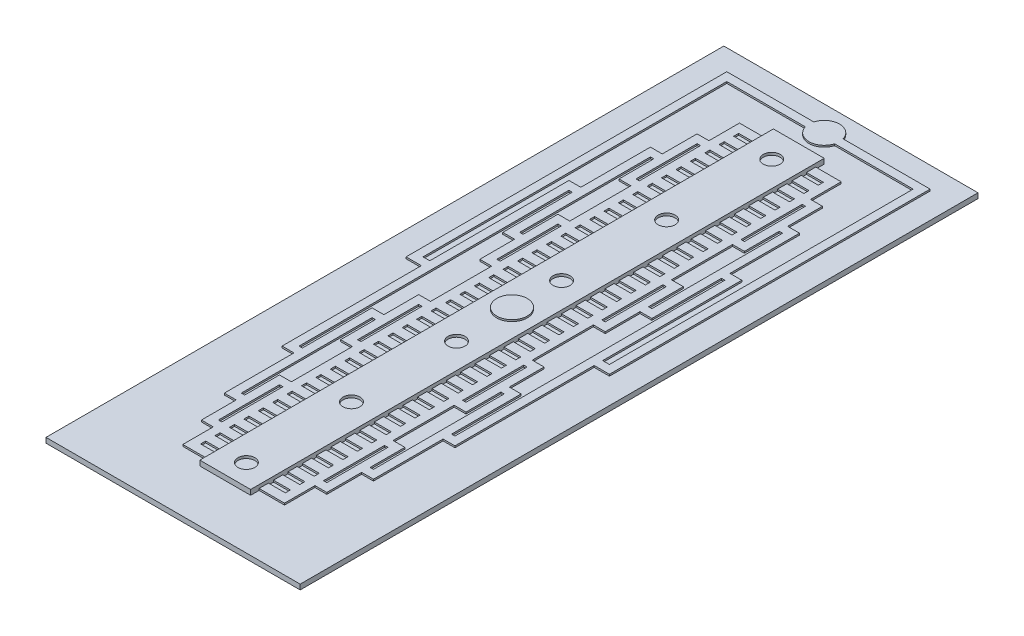
SolidWorks part; units mm, degrees
ref_plane "Front Plane" through (0, 0, 0) normal (0, 0, 1) x (1, 0, 0)
ref_plane "Top Plane" through (0, 0, 0) normal (0, 1, 0) x (1, 0, 0)
ref_plane "Right Plane" through (0, 0, 0) normal (1, 0, 0) x (0, 0, -1)
sketch "Sketch2" plane through (0, 0, 0) normal (0, 1, 0) x (1, 0, 0)
  line L1 (-7.5, 20) -> (7.5, 20)
  line L2 (-7.5, 20) -> (-7.5, -20)
  line L3 (-7.5, -20) -> (7.5, -20)
  line L4 (7.5, 20) -> (7.5, -20)
  line L5 (-7.5, 20) -> (7.5, -20) construction
  line L6 (-7.5, -20) -> (7.5, 20) construction
  point P0 (0, 0)
extrude "Boss-Extrude1" add sketch "Sketch2" along normal blind 0.3
sketch "Sketch3" plane through (0, 0.3, 0) normal (0, 1, 0) x (1, 0, 0)
  line L1 (-1.5, 16.925) -> (1.5, 16.925)
  line L2 (-1.5, 16.925) -> (-1.5, -16.925)
  line L3 (-1.5, -16.925) -> (1.5, -16.925)
  line L4 (1.5, 16.925) -> (1.5, -16.925)
  line L5 (-1.5, 16.925) -> (1.5, -16.925) construction
  line L6 (-1.5, -16.925) -> (1.5, 16.925) construction
  point P0 (0, 0)
extrude "Boss-Extrude2" add sketch "Sketch3" along normal blind 0.3
sketch "Sketch4" plane through (0, 0.3, 0) normal (0, 1, 0) x (1, 0, 0)
  line L0 (0, 19.2283) -> (0, -19.2283) construction
  line L1 (-7.7467, 0) -> (7.7467, 0) construction
  line L2 (1.5, 16.425) -> (3, 16.425)
  line L3 (1.5, 16.425) -> (1.5, -16.425)
  line L4 (3, 16.425) -> (3, -16.425)
  line L5 (1.5, -16.425) -> (3, -16.425)
  line L6 (1.5, -16.925) -> (1.5, 16.925) construction
  line L7 (-1.5, -16.425) -> (-3, -16.425)
  line L8 (-1.5, 16.425) -> (-1.5, -16.425)
  line L9 (-3, 16.425) -> (-3, -16.425)
  line L10 (-1.5, 16.425) -> (-3, 16.425)
  point P3 (3, 0)
  point P4 (0, 0)
  point P8 (0, 0)
extrude "Boss-Extrude3" add sketch "Sketch4" along normal blind 0.1
sketch "Sketch5" plane through (0, 0.4, 0) normal (0, 1, 0) x (1, 0, 0)
  line L0 (1.5, 16.425) -> (1.5, -16.425) construction
  line L1 (1.5, 15.875) -> (2.5, 15.875)
  line L2 (1.5, 15.875) -> (1.5, 15.575)
  line L3 (2.5, 15.875) -> (2.5, 15.575)
  line L4 (1.5, 15.575) -> (2.5, 15.575)
  line L5 (-1.5, 15.875) -> (-1.5, 15.575)
  line L6 (-2.5, 15.875) -> (-1.5, 15.875)
  line L7 (-2.5, 15.875) -> (-2.5, 15.575)
  line L8 (-2.5, 15.575) -> (-1.5, 15.575)
  line L9 (-1.5, 15.025) -> (-1.5, 14.725)
  line L10 (-2.5, 15.025) -> (-1.5, 15.025)
  line L11 (-2.5, 15.025) -> (-2.5, 14.725)
  line L12 (-2.5, 14.725) -> (-1.5, 14.725)
  line L13 (-1.5, 14.175) -> (-1.5, 13.875)
  line L14 (-2.5, 14.175) -> (-1.5, 14.175)
  line L15 (-2.5, 14.175) -> (-2.5, 13.875)
  line L16 (-2.5, 13.875) -> (-1.5, 13.875)
  line L17 (-1.5, 13.325) -> (-1.5, 13.025)
  line L18 (-2.5, 13.325) -> (-1.5, 13.325)
  line L19 (-2.5, 13.325) -> (-2.5, 13.025)
  line L20 (-2.5, 13.025) -> (-1.5, 13.025)
  line L21 (-1.5, 12.475) -> (-1.5, 12.175)
  line L22 (-2.5, 12.475) -> (-1.5, 12.475)
  line L23 (-2.5, 12.475) -> (-2.5, 12.175)
  line L24 (-2.5, 12.175) -> (-1.5, 12.175)
  line L25 (-1.5, 11.625) -> (-1.5, 11.325)
  line L26 (-2.5, 11.625) -> (-1.5, 11.625)
  line L27 (-2.5, 11.625) -> (-2.5, 11.325)
  line L28 (-2.5, 11.325) -> (-1.5, 11.325)
  line L29 (-1.5, 10.775) -> (-1.5, 10.475)
  line L30 (-2.5, 10.775) -> (-1.5, 10.775)
  line L31 (-2.5, 10.775) -> (-2.5, 10.475)
  line L32 (-2.5, 10.475) -> (-1.5, 10.475)
  line L33 (-1.5, 9.925) -> (-1.5, 9.625)
  line L34 (-2.5, 9.925) -> (-1.5, 9.925)
  line L35 (-2.5, 9.925) -> (-2.5, 9.625)
  line L36 (-2.5, 9.625) -> (-1.5, 9.625)
  line L37 (-1.5, 9.075) -> (-1.5, 8.775)
  line L38 (-2.5, 9.075) -> (-1.5, 9.075)
  line L39 (-2.5, 9.075) -> (-2.5, 8.775)
  line L40 (-2.5, 8.775) -> (-1.5, 8.775)
  line L41 (-1.5, 8.225) -> (-1.5, 7.925)
  line L42 (-2.5, 8.225) -> (-1.5, 8.225)
  line L43 (-2.5, 8.225) -> (-2.5, 7.925)
  line L44 (-2.5, 7.925) -> (-1.5, 7.925)
  line L45 (-1.5, 7.375) -> (-1.5, 7.075)
  line L46 (-2.5, 7.375) -> (-1.5, 7.375)
  line L47 (-2.5, 7.375) -> (-2.5, 7.075)
  line L48 (-2.5, 7.075) -> (-1.5, 7.075)
  line L49 (-1.5, 6.525) -> (-1.5, 6.225)
  line L50 (-2.5, 6.525) -> (-1.5, 6.525)
  line L51 (-2.5, 6.525) -> (-2.5, 6.225)
  line L52 (-2.5, 6.225) -> (-1.5, 6.225)
  line L53 (-1.5, 5.675) -> (-1.5, 5.375)
  line L54 (-2.5, 5.675) -> (-1.5, 5.675)
  line L55 (-2.5, 5.675) -> (-2.5, 5.375)
  line L56 (-2.5, 5.375) -> (-1.5, 5.375)
  line L57 (-1.5, 4.825) -> (-1.5, 4.525)
  line L58 (-2.5, 4.825) -> (-1.5, 4.825)
  line L59 (-2.5, 4.825) -> (-2.5, 4.525)
  line L60 (-2.5, 4.525) -> (-1.5, 4.525)
  line L61 (-1.5, 3.975) -> (-1.5, 3.675)
  line L62 (-2.5, 3.975) -> (-1.5, 3.975)
  line L63 (-2.5, 3.975) -> (-2.5, 3.675)
  line L64 (-2.5, 3.675) -> (-1.5, 3.675)
  line L65 (-1.5, 3.125) -> (-1.5, 2.825)
  line L66 (-2.5, 3.125) -> (-1.5, 3.125)
  line L67 (-2.5, 3.125) -> (-2.5, 2.825)
  line L68 (-2.5, 2.825) -> (-1.5, 2.825)
  line L69 (-1.5, 2.275) -> (-1.5, 1.975)
  line L70 (-2.5, 2.275) -> (-1.5, 2.275)
  line L71 (-2.5, 2.275) -> (-2.5, 1.975)
  line L72 (-2.5, 1.975) -> (-1.5, 1.975)
  line L73 (-1.5, 1.425) -> (-1.5, 1.125)
  line L74 (-2.5, 1.425) -> (-1.5, 1.425)
  line L75 (-2.5, 1.425) -> (-2.5, 1.125)
  line L76 (-2.5, 1.125) -> (-1.5, 1.125)
  line L77 (-1.5, 0.575) -> (-1.5, 0.275)
  line L78 (-2.5, 0.575) -> (-1.5, 0.575)
  line L79 (-2.5, 0.575) -> (-2.5, 0.275)
  line L80 (-2.5, 0.275) -> (-1.5, 0.275)
  line L81 (-1.5, -0.275) -> (-1.5, -0.575)
  line L82 (-2.5, -0.275) -> (-1.5, -0.275)
  line L83 (-2.5, -0.275) -> (-2.5, -0.575)
  line L84 (-2.5, -0.575) -> (-1.5, -0.575)
  line L85 (-1.5, -1.125) -> (-1.5, -1.425)
  line L86 (-2.5, -1.125) -> (-1.5, -1.125)
  line L87 (-2.5, -1.125) -> (-2.5, -1.425)
  line L88 (-2.5, -1.425) -> (-1.5, -1.425)
  line L89 (-1.5, -1.975) -> (-1.5, -2.275)
  line L90 (-2.5, -1.975) -> (-1.5, -1.975)
  line L91 (-2.5, -1.975) -> (-2.5, -2.275)
  line L92 (-2.5, -2.275) -> (-1.5, -2.275)
  line L93 (-1.5, -2.825) -> (-1.5, -3.125)
  line L94 (-2.5, -2.825) -> (-1.5, -2.825)
  line L95 (-2.5, -2.825) -> (-2.5, -3.125)
  line L96 (-2.5, -3.125) -> (-1.5, -3.125)
  line L97 (-1.5, -3.675) -> (-1.5, -3.975)
  line L98 (-2.5, -3.675) -> (-1.5, -3.675)
  line L99 (-2.5, -3.675) -> (-2.5, -3.975)
  line L100 (-2.5, -3.975) -> (-1.5, -3.975)
  line L101 (-1.5, -4.525) -> (-1.5, -4.825)
  line L102 (-2.5, -4.525) -> (-1.5, -4.525)
  line L103 (-2.5, -4.525) -> (-2.5, -4.825)
  line L104 (-2.5, -4.825) -> (-1.5, -4.825)
  line L105 (-1.5, -5.375) -> (-1.5, -5.675)
  line L106 (-2.5, -5.375) -> (-1.5, -5.375)
  line L107 (-2.5, -5.375) -> (-2.5, -5.675)
  line L108 (-2.5, -5.675) -> (-1.5, -5.675)
  line L109 (-1.5, -6.225) -> (-1.5, -6.525)
  line L110 (-2.5, -6.225) -> (-1.5, -6.225)
  line L111 (-2.5, -6.225) -> (-2.5, -6.525)
  line L112 (-2.5, -6.525) -> (-1.5, -6.525)
  line L113 (-1.5, -7.075) -> (-1.5, -7.375)
  line L114 (-2.5, -7.075) -> (-1.5, -7.075)
  line L115 (-2.5, -7.075) -> (-2.5, -7.375)
  line L116 (-2.5, -7.375) -> (-1.5, -7.375)
  line L117 (-1.5, -7.925) -> (-1.5, -8.225)
  line L118 (-2.5, -7.925) -> (-1.5, -7.925)
  line L119 (-2.5, -7.925) -> (-2.5, -8.225)
  line L120 (-2.5, -8.225) -> (-1.5, -8.225)
  line L121 (-1.5, -8.775) -> (-1.5, -9.075)
  line L122 (-2.5, -8.775) -> (-1.5, -8.775)
  line L123 (-2.5, -8.775) -> (-2.5, -9.075)
  line L124 (-2.5, -9.075) -> (-1.5, -9.075)
  line L125 (-1.5, -9.625) -> (-1.5, -9.925)
  line L126 (-2.5, -9.625) -> (-1.5, -9.625)
  line L127 (-2.5, -9.625) -> (-2.5, -9.925)
  line L128 (-2.5, -9.925) -> (-1.5, -9.925)
  line L129 (-1.5, -10.475) -> (-1.5, -10.775)
  line L130 (-2.5, -10.475) -> (-1.5, -10.475)
  line L131 (-2.5, -10.475) -> (-2.5, -10.775)
  line L132 (-2.5, -10.775) -> (-1.5, -10.775)
  line L133 (-1.5, -11.325) -> (-1.5, -11.625)
  line L134 (-2.5, -11.325) -> (-1.5, -11.325)
  line L135 (-2.5, -11.325) -> (-2.5, -11.625)
  line L136 (-2.5, -11.625) -> (-1.5, -11.625)
  line L137 (-1.5, -12.175) -> (-1.5, -12.475)
  line L138 (-2.5, -12.175) -> (-1.5, -12.175)
  line L139 (-2.5, -12.175) -> (-2.5, -12.475)
  line L140 (-2.5, -12.475) -> (-1.5, -12.475)
  line L141 (-1.5, -13.025) -> (-1.5, -13.325)
  line L142 (-2.5, -13.025) -> (-1.5, -13.025)
  line L143 (-2.5, -13.025) -> (-2.5, -13.325)
  line L144 (-2.5, -13.325) -> (-1.5, -13.325)
  line L145 (-1.5, -13.875) -> (-1.5, -14.175)
  line L146 (-2.5, -13.875) -> (-1.5, -13.875)
  line L147 (-2.5, -13.875) -> (-2.5, -14.175)
  line L148 (-2.5, -14.175) -> (-1.5, -14.175)
  line L149 (-1.5, -14.725) -> (-1.5, -15.025)
  line L150 (-2.5, -14.725) -> (-1.5, -14.725)
  line L151 (-2.5, -14.725) -> (-2.5, -15.025)
  line L152 (-2.5, -15.025) -> (-1.5, -15.025)
  line L153 (-1.5, -15.575) -> (-1.5, -15.875)
  line L154 (-2.5, -15.575) -> (-1.5, -15.575)
  line L155 (-2.5, -15.575) -> (-2.5, -15.875)
  line L156 (-2.5, -15.875) -> (-1.5, -15.875)
  line L157 (2.5, 15.025) -> (2.5, 14.725)
  line L158 (1.5, 15.025) -> (2.5, 15.025)
  line L159 (1.5, 15.025) -> (1.5, 14.725)
  line L160 (1.5, 14.725) -> (2.5, 14.725)
  line L161 (2.5, 14.175) -> (2.5, 13.875)
  line L162 (1.5, 14.175) -> (2.5, 14.175)
  line L163 (1.5, 14.175) -> (1.5, 13.875)
  line L164 (1.5, 13.875) -> (2.5, 13.875)
  line L165 (2.5, 13.325) -> (2.5, 13.025)
  line L166 (1.5, 13.325) -> (2.5, 13.325)
  line L167 (1.5, 13.325) -> (1.5, 13.025)
  line L168 (1.5, 13.025) -> (2.5, 13.025)
  line L169 (2.5, 12.475) -> (2.5, 12.175)
  line L170 (1.5, 12.475) -> (2.5, 12.475)
  line L171 (1.5, 12.475) -> (1.5, 12.175)
  line L172 (1.5, 12.175) -> (2.5, 12.175)
  line L173 (2.5, 11.625) -> (2.5, 11.325)
  line L174 (1.5, 11.625) -> (2.5, 11.625)
  line L175 (1.5, 11.625) -> (1.5, 11.325)
  line L176 (1.5, 11.325) -> (2.5, 11.325)
  line L177 (2.5, 10.775) -> (2.5, 10.475)
  line L178 (1.5, 10.775) -> (2.5, 10.775)
  line L179 (1.5, 10.775) -> (1.5, 10.475)
  line L180 (1.5, 10.475) -> (2.5, 10.475)
  line L181 (2.5, 9.925) -> (2.5, 9.625)
  line L182 (1.5, 9.925) -> (2.5, 9.925)
  line L183 (1.5, 9.925) -> (1.5, 9.625)
  line L184 (1.5, 9.625) -> (2.5, 9.625)
  line L185 (2.5, 9.075) -> (2.5, 8.775)
  line L186 (1.5, 9.075) -> (2.5, 9.075)
  line L187 (1.5, 9.075) -> (1.5, 8.775)
  line L188 (1.5, 8.775) -> (2.5, 8.775)
  line L189 (2.5, 8.225) -> (2.5, 7.925)
  line L190 (1.5, 8.225) -> (2.5, 8.225)
  line L191 (1.5, 8.225) -> (1.5, 7.925)
  line L192 (1.5, 7.925) -> (2.5, 7.925)
  line L193 (2.5, 7.375) -> (2.5, 7.075)
  line L194 (1.5, 7.375) -> (2.5, 7.375)
  line L195 (1.5, 7.375) -> (1.5, 7.075)
  line L196 (1.5, 7.075) -> (2.5, 7.075)
  line L197 (2.5, 6.525) -> (2.5, 6.225)
  line L198 (1.5, 6.525) -> (2.5, 6.525)
  line L199 (1.5, 6.525) -> (1.5, 6.225)
  line L200 (1.5, 6.225) -> (2.5, 6.225)
  line L201 (2.5, 5.675) -> (2.5, 5.375)
  line L202 (1.5, 5.675) -> (2.5, 5.675)
  line L203 (1.5, 5.675) -> (1.5, 5.375)
  line L204 (1.5, 5.375) -> (2.5, 5.375)
  line L205 (2.5, 4.825) -> (2.5, 4.525)
  line L206 (1.5, 4.825) -> (2.5, 4.825)
  line L207 (1.5, 4.825) -> (1.5, 4.525)
  line L208 (1.5, 4.525) -> (2.5, 4.525)
  line L209 (2.5, 3.975) -> (2.5, 3.675)
  line L210 (1.5, 3.975) -> (2.5, 3.975)
  line L211 (1.5, 3.975) -> (1.5, 3.675)
  line L212 (1.5, 3.675) -> (2.5, 3.675)
  line L213 (2.5, 3.125) -> (2.5, 2.825)
  line L214 (1.5, 3.125) -> (2.5, 3.125)
  line L215 (1.5, 3.125) -> (1.5, 2.825)
  line L216 (1.5, 2.825) -> (2.5, 2.825)
  line L217 (2.5, 2.275) -> (2.5, 1.975)
  line L218 (1.5, 2.275) -> (2.5, 2.275)
  line L219 (1.5, 2.275) -> (1.5, 1.975)
  line L220 (1.5, 1.975) -> (2.5, 1.975)
  line L221 (2.5, 1.425) -> (2.5, 1.125)
  line L222 (1.5, 1.425) -> (2.5, 1.425)
  line L223 (1.5, 1.425) -> (1.5, 1.125)
  line L224 (1.5, 1.125) -> (2.5, 1.125)
  line L225 (2.5, 0.575) -> (2.5, 0.275)
  line L226 (1.5, 0.575) -> (2.5, 0.575)
  line L227 (1.5, 0.575) -> (1.5, 0.275)
  line L228 (1.5, 0.275) -> (2.5, 0.275)
  line L229 (2.5, -0.275) -> (2.5, -0.575)
  line L230 (1.5, -0.275) -> (2.5, -0.275)
  line L231 (1.5, -0.275) -> (1.5, -0.575)
  line L232 (1.5, -0.575) -> (2.5, -0.575)
  line L233 (2.5, -1.125) -> (2.5, -1.425)
  line L234 (1.5, -1.125) -> (2.5, -1.125)
  line L235 (1.5, -1.125) -> (1.5, -1.425)
  line L236 (1.5, -1.425) -> (2.5, -1.425)
  line L237 (2.5, -1.975) -> (2.5, -2.275)
  line L238 (1.5, -1.975) -> (2.5, -1.975)
  line L239 (1.5, -1.975) -> (1.5, -2.275)
  line L240 (1.5, -2.275) -> (2.5, -2.275)
  line L241 (2.5, -2.825) -> (2.5, -3.125)
  line L242 (1.5, -2.825) -> (2.5, -2.825)
  line L243 (1.5, -2.825) -> (1.5, -3.125)
  line L244 (1.5, -3.125) -> (2.5, -3.125)
  line L245 (2.5, -3.675) -> (2.5, -3.975)
  line L246 (1.5, -3.675) -> (2.5, -3.675)
  line L247 (1.5, -3.675) -> (1.5, -3.975)
  line L248 (1.5, -3.975) -> (2.5, -3.975)
  line L249 (2.5, -4.525) -> (2.5, -4.825)
  line L250 (1.5, -4.525) -> (2.5, -4.525)
  line L251 (1.5, -4.525) -> (1.5, -4.825)
  line L252 (1.5, -4.825) -> (2.5, -4.825)
  line L253 (2.5, -5.375) -> (2.5, -5.675)
  line L254 (1.5, -5.375) -> (2.5, -5.375)
  line L255 (1.5, -5.375) -> (1.5, -5.675)
  line L256 (1.5, -5.675) -> (2.5, -5.675)
  line L257 (2.5, -6.225) -> (2.5, -6.525)
  line L258 (1.5, -6.225) -> (2.5, -6.225)
  line L259 (1.5, -6.225) -> (1.5, -6.525)
  line L260 (1.5, -6.525) -> (2.5, -6.525)
  line L261 (2.5, -7.075) -> (2.5, -7.375)
  line L262 (1.5, -7.075) -> (2.5, -7.075)
  line L263 (1.5, -7.075) -> (1.5, -7.375)
  line L264 (1.5, -7.375) -> (2.5, -7.375)
  line L265 (2.5, -7.925) -> (2.5, -8.225)
  line L266 (1.5, -7.925) -> (2.5, -7.925)
  line L267 (1.5, -7.925) -> (1.5, -8.225)
  line L268 (1.5, -8.225) -> (2.5, -8.225)
  line L269 (2.5, -8.775) -> (2.5, -9.075)
  line L270 (1.5, -8.775) -> (2.5, -8.775)
  line L271 (1.5, -8.775) -> (1.5, -9.075)
  line L272 (1.5, -9.075) -> (2.5, -9.075)
  line L273 (2.5, -9.625) -> (2.5, -9.925)
  line L274 (1.5, -9.625) -> (2.5, -9.625)
  line L275 (1.5, -9.625) -> (1.5, -9.925)
  line L276 (1.5, -9.925) -> (2.5, -9.925)
  line L277 (2.5, -10.475) -> (2.5, -10.775)
  line L278 (1.5, -10.475) -> (2.5, -10.475)
  line L279 (1.5, -10.475) -> (1.5, -10.775)
  line L280 (1.5, -10.775) -> (2.5, -10.775)
  line L281 (2.5, -11.325) -> (2.5, -11.625)
  line L282 (1.5, -11.325) -> (2.5, -11.325)
  line L283 (1.5, -11.325) -> (1.5, -11.625)
  line L284 (1.5, -11.625) -> (2.5, -11.625)
  line L285 (2.5, -12.175) -> (2.5, -12.475)
  line L286 (1.5, -12.175) -> (2.5, -12.175)
  line L287 (1.5, -12.175) -> (1.5, -12.475)
  line L288 (1.5, -12.475) -> (2.5, -12.475)
  line L289 (2.5, -13.025) -> (2.5, -13.325)
  line L290 (1.5, -13.025) -> (2.5, -13.025)
  line L291 (1.5, -13.025) -> (1.5, -13.325)
  line L292 (1.5, -13.325) -> (2.5, -13.325)
  line L293 (2.5, -13.875) -> (2.5, -14.175)
  line L294 (1.5, -13.875) -> (2.5, -13.875)
  line L295 (1.5, -13.875) -> (1.5, -14.175)
  line L296 (1.5, -14.175) -> (2.5, -14.175)
  line L297 (2.5, -14.725) -> (2.5, -15.025)
  line L298 (1.5, -14.725) -> (2.5, -14.725)
  line L299 (1.5, -14.725) -> (1.5, -15.025)
  line L300 (1.5, -15.025) -> (2.5, -15.025)
  line L301 (2.5, -15.575) -> (2.5, -15.875)
  line L302 (1.5, -15.575) -> (2.5, -15.575)
  line L303 (1.5, -15.575) -> (1.5, -15.875)
  line L304 (1.5, -15.875) -> (2.5, -15.875)
  point P0 (1.5, 15.875)
  dimension "D1" = 0.55
  dimension "D2" = 2
  dimension "D3" = 38
extrude "Cut-Extrude1" cut sketch "Sketch5" against normal blind 0.1
sketch "Sketch6" plane through (0, 0.3, 0) normal (0, 1, 0) x (1, 0, 0)
  line L0 (-7.9902, 0) -> (7.9902, 0) construction
  line L1 (0, -20.3947) -> (0, 20.3947) construction
  line L2 (1.5, 16.925) -> (-1.5, 16.925) construction
  line L3 (-6, 18.675) -> (6, 18.675)
  line L4 (-5.5, 18.175) -> (5.5, 18.175)
  line L5 (-6, 18.675) -> (-6, -0.25)
  line L6 (-5.5, 18.175) -> (-5.5, 0.25)
  line L7 (-6, -0.25) -> (-5.1, -0.25)
  line L8 (-5.5, 0.25) -> (-5.1, 0.25)
  line L9 (-3, 16.425) -> (-3, -16.425) construction
  line L10 (-3, 14.6215) -> (-3.7, 14.6215)
  line L11 (-3, 14.1215) -> (-3.2, 14.1215)
  line L12 (-3, 16.425) -> (-3, -16.425) construction
  line L13 (-3, 10.0144) -> (-3.7, 10.0144)
  line L14 (-3.7, 12.0679) -> (-3.7, 10.0144)
  line L15 (-3.7, 14.6215) -> (-3.7, 12.5679)
  line L16 (-3.2, 14.1215) -> (-3.2, 10.5144)
  line L17 (-3.2, 10.5144) -> (-3, 10.5144)
  line L18 (-3, 12.3179) -> (-3.8547, 12.3179) construction
  line L19 (-3, 6.4073) -> (-3.7, 6.4073)
  line L20 (-3, 5.9073) -> (-3.2, 5.9073)
  line L21 (-3, 1.8003) -> (-3.7, 1.8003)
  line L22 (-3, 2.3003) -> (-3.2, 2.3003)
  line L23 (-3.2, 2.3003) -> (-3.2, 5.9073)
  line L24 (-3.7, 4.3538) -> (-3.7, 6.4073)
  line L25 (-3.7, 1.8003) -> (-3.7, 3.8538)
  line L26 (-3, 4.1038) -> (-3.8547, 4.1038) construction
  line L27 (-3, -1.8068) -> (-3.7, -1.8068)
  line L28 (-3, -2.3068) -> (-3.2, -2.3068)
  line L29 (-3, -6.4139) -> (-3.7, -6.4139)
  line L30 (-3.7, -6.4139) -> (-3.7, -4.3604)
  line L31 (-3.7, -1.8068) -> (-3.7, -3.8604)
  line L32 (-3, -5.9139) -> (-3.2, -5.9139)
  line L33 (-3.2, -5.9139) -> (-3.2, -2.3068)
  line L34 (-3, -4.1104) -> (-3.9544, -4.1104) construction
  line L35 (-3, -10.021) -> (-3.7, -10.021)
  line L36 (-3.7, -10.021) -> (-3.7, -12.0745)
  line L37 (-3, -10.521) -> (-3.2, -10.521)
  line L38 (-3, -14.628) -> (-3.7, -14.628)
  line L39 (-3.7, -14.628) -> (-3.7, -12.5745)
  line L40 (-3, -14.128) -> (-3.2, -14.128)
  line L41 (-3.2, -14.128) -> (-3.2, -10.521)
  line L42 (-3, -12.3245) -> (-3.7601, -12.3245) construction
  line L43 (-3.7, 12.5679) -> (-4.4, 12.5679)
  line L44 (-3.7, 12.0679) -> (-3.9, 12.0679)
  line L45 (-4.4, 12.5679) -> (-4.4, 8.4609)
  line L46 (-4.4, 7.9609) -> (-4.4, 3.8538)
  line L47 (-4.4, 3.8538) -> (-3.7, 3.8538)
  line L48 (-3.7, 4.3538) -> (-3.9, 4.3538)
  line L49 (-3.9, 4.3538) -> (-3.9, 12.0679)
  line L50 (-3.7, -3.8604) -> (-4.4, -3.8604)
  line L51 (-4.4, -3.8604) -> (-4.4, -7.9674)
  line L52 (-4.4, -12.5745) -> (-3.7, -12.5745)
  line L53 (-4.4, -12.5745) -> (-4.4, -8.4674)
  line L54 (-3.7, -4.3604) -> (-3.9, -4.3604)
  line L55 (-3.9, -4.3604) -> (-3.9, -12.0745)
  line L56 (-3.9, -12.0745) -> (-3.7, -12.0745)
  line L57 (-3, -8.2174) -> (-4.9354, -8.2174) construction
  line L58 (-3, 8.2109) -> (-4.9354, 8.2109) construction
  line L59 (-4.4, 8.4609) -> (-5.1, 8.4609)
  line L60 (-5.1, 8.4609) -> (-5.1, 0.25)
  line L61 (-4.4, 7.9609) -> (-4.6, 7.9609)
  line L62 (-4.6, 7.9609) -> (-4.6, -7.9674)
  line L63 (-4.6, -7.9674) -> (-4.4, -7.9674)
  line L64 (-4.4, -8.4674) -> (-5.1, -8.4674)
  line L65 (-5.1, -8.4674) -> (-5.1, -0.25)
  line L66 (3, -14.628) -> (3.7, -14.628)
  line L67 (3, -14.128) -> (3.2, -14.128)
  line L68 (3.7, -14.628) -> (3.7, -12.5745)
  line L69 (4.4, -12.5745) -> (3.7, -12.5745)
  line L70 (3.9, -12.0745) -> (3.7, -12.0745)
  line L71 (3.2, -14.128) -> (3.2, -10.521)
  line L72 (3, -10.521) -> (3.2, -10.521)
  line L73 (3.7, -10.021) -> (3.7, -12.0745)
  line L74 (3, -10.021) -> (3.7, -10.021)
  line L75 (4.4, -12.5745) -> (4.4, -8.4674)
  line L76 (4.4, -8.4674) -> (5.1, -8.4674)
  line L77 (4.6, -7.9674) -> (4.4, -7.9674)
  line L78 (3, -6.4139) -> (3.7, -6.4139)
  line L79 (3, -5.9139) -> (3.2, -5.9139)
  line L80 (3.7, -6.4139) -> (3.7, -4.3604)
  line L81 (3.9, -4.3604) -> (3.9, -12.0745)
  line L82 (3.7, -4.3604) -> (3.9, -4.3604)
  line L83 (4.4, -3.8604) -> (4.4, -7.9674)
  line L84 (3.7, -3.8604) -> (4.4, -3.8604)
  line L85 (3.2, -5.9139) -> (3.2, -2.3068)
  line L86 (3, -2.3068) -> (3.2, -2.3068)
  line L87 (3.7, -1.8068) -> (3.7, -3.8604)
  line L88 (3, -1.8068) -> (3.7, -1.8068)
  line L89 (5.1, -8.4674) -> (5.1, -0.25)
  line L90 (6, -0.25) -> (5.1, -0.25)
  line L91 (5.5, 0.25) -> (5.1, 0.25)
  line L92 (3, 1.8003) -> (3.7, 1.8003)
  line L93 (3, 2.3003) -> (3.2, 2.3003)
  line L94 (3.7, 1.8003) -> (3.7, 3.8538)
  line L95 (4.4, 3.8538) -> (3.7, 3.8538)
  line L96 (3.7, 4.3538) -> (3.9, 4.3538)
  line L97 (3.2, 2.3003) -> (3.2, 5.9073)
  line L98 (3, 5.9073) -> (3.2, 5.9073)
  line L99 (3.7, 4.3538) -> (3.7, 6.4073)
  line L100 (3, 6.4073) -> (3.7, 6.4073)
  line L101 (4.4, 7.9609) -> (4.4, 3.8538)
  line L102 (4.6, 7.9609) -> (4.6, -7.9674)
  line L103 (4.4, 7.9609) -> (4.6, 7.9609)
  line L104 (5.1, 8.4609) -> (5.1, 0.25)
  line L105 (4.4, 8.4609) -> (5.1, 8.4609)
  line L106 (3, 10.0144) -> (3.7, 10.0144)
  line L107 (3.2, 10.5144) -> (3, 10.5144)
  line L108 (3.7, 12.0679) -> (3.7, 10.0144)
  line L109 (4.4, 12.5679) -> (4.4, 8.4609)
  line L110 (3.9, 4.3538) -> (3.9, 12.0679)
  line L111 (3.7, 12.0679) -> (3.9, 12.0679)
  line L112 (3.7, 12.5679) -> (4.4, 12.5679)
  line L113 (3.2, 14.1215) -> (3.2, 10.5144)
  line L114 (3, 14.1215) -> (3.2, 14.1215)
  line L115 (3.7, 14.6215) -> (3.7, 12.5679)
  line L116 (3, 14.6215) -> (3.7, 14.6215)
  line L117 (6, 18.675) -> (6, -0.25)
  line L118 (5.5, 18.175) -> (5.5, 0.25)
  circle A0 centre (0, 18.425) radius 0.9
  point P0 (0, 16.925)
  point P3 (-6, 0)
  point P4 (0, 0)
  point P8 (0, 0)
  point P9 (0, 18.425)
  point P14 (0, 18.675)
  point P15 (0, 18.175)
  point P19 (0, 18.675)
  point P22 (0, 18.175)
  point P24 (-6, 0)
  point P25 (-3, 16.425)
  point P27 (-3, 14.6215)
  point P28 (-3, 14.1215)
  point P29 (-3, 15.3982)
  point P32 (-3, 14.3715)
  point P33 (-3, 13.3447)
  point P34 (-3, 12.3179)
  point P35 (-3, 11.2912)
  point P36 (-3, 10.2644)
  point P37 (-3, 9.2376)
  point P38 (-3, 8.2109)
  point P39 (-3, 7.1841)
  point P40 (-3, 6.1573)
  point P41 (-3, 5.1306)
  point P42 (-3, 4.1038)
  point P43 (-3, 3.077)
  point P44 (-3, 2.0503)
  point P45 (-3, 1.0235)
  point P46 (-3, -0.0033)
  point P47 (-3, -1.0301)
  point P48 (-3, -2.0568)
  point P49 (-3, -3.0836)
  point P50 (-3, -4.1104)
  point P51 (-3, -5.1371)
  point P52 (-3, -6.1639)
  point P53 (-3, -7.1907)
  point P54 (-3, -8.2174)
  point P55 (-3, -9.2442)
  point P56 (-3, -10.271)
  point P57 (-3, -11.2977)
  point P58 (-3, -12.3245)
  point P59 (-3, -13.3513)
  point P60 (-3, -14.378)
  point P61 (-3, -15.4048)
  point P62 (-3, -16.4316)
  point P69 (-3, 10.0144)
  point P70 (-3, 10.5144)
  point P81 (-3.7, 12.3179)
  point P82 (-3, 5.9073)
  point P83 (-3, 6.4073)
  point P88 (-3, 1.8003)
  point P89 (-3, 2.3003)
  point P98 (-3.7, 4.1038)
  point P99 (-3, -2.3068)
  point P100 (-3, -1.8068)
  point P105 (-3, -6.4139)
  point P106 (-3, -5.9139)
  point P115 (-5.5, 0)
  point P116 (-3, -10.521)
  point P117 (-3, -10.021)
  point P123 (-3, -14.628)
  point P124 (-3, -14.128)
  point P132 (-4.4, -8.2174)
  point P150 (-4.4, 8.2109)
  point P215 (-3.7, -4.1104)
  point P216 (-3.7, -12.3245)
  point P222 (-4.4, -7.9674)
  line M97 (-3, -16.425) -> (-3, 16.425)
  line M103 (3, 16.425) -> (3, -16.425)
  dimension "D2" = 0.25
  dimension "D1" = 1.5
  dimension "D3" = 0.25
  dimension "D4" = 0.25
  dimension "D5" = 33
  dimension "D6" = 0.25
  dimension "D7" = 0.25
  dimension "D8" = 0.25
  dimension "D9" = 0.25
  dimension ".25" = 0.25
  dimension "D10" = 0.25
  dimension "D11" = 0.25
  dimension "D12" = 0.25
  dimension "D13" = 0.25
  dimension "D14" = 0.25
  dimension "D15" = 0.25
  dimension "D16" = 0.25
  dimension "D17" = 0.25
  dimension "D18" = 0.25
  dimension "D19" = 0.25
  dimension "D20" = 0.25
  dimension "D21" = 0.25
  dimension "D22" = 0.25
  dimension "D23" = 0.25
  dimension "D24" = 0.25
  dimension "D25" = 0.25
  dimension "D26" = 0.25
  dimension "D27" = 0.25
  dimension "D28" = 0.25
  dimension "D29" = 0.25
  dimension "D30" = 0.25
  dimension "D31" = 0.25
  dimension "D32" = 0.25
  dimension "D33" = 0.25
extrude "Boss-Extrude4" add sketch "Sketch6" along normal blind 0.1 contours A0 L4 L118 L91 L104 L105 L109 L112 L115 L116 L114 L113 L107 L106 L108 L111 L110 L96 L99 L100 L98 L97 L93 L92 L94 L95 L101 L103 L102 L77 L83 L84 L87 L88 L86 L85 L79 L78 L80 L82 L81 L70 L73 L74 M103 | A0 L3 L5 L7 L65 L64 L53 L52 L39 L38 L40 L41 L37 L35 L36 L56 L55 L54 L30 L29 L32 L33 L28 L27 L31 L50 L51 L63 L62 L61 L46 L47 L25 L21 L22 L23 L20 L19 L24 L48 L49 L44 L14 L13 M97 | L4 A0 L3 | L3 A0 | L4 A0 region at (-3.4323, 0.3, -18.338) region at (0, 0.3, -18.9452) region at (0, 0.3, -18.425) region at (3.4323, 0.3, -18.338) region at (0, 0.3, -17.9048)
sketch "Sketch7" plane through (0, 0.6, 0) normal (0, 1, 0) x (1, 0, 0)
  circle A0 centre (0, 0) radius 0.9
extrude "Boss-Extrude5" add sketch "Sketch7" along normal blind 0.1 contours A0
sketch "Sketch8" plane through (0, 0.6, 0) normal (0, 1, 0) x (1, 0, 0)
  circle A0 centre (0, 15.3265) radius 0.5
  circle A1 centre (0, 9.1265) radius 0.5
  circle A2 centre (0, 2.9265) radius 0.5
  circle A3 centre (0, -3.2735) radius 0.5
  circle A4 centre (0, -9.4735) radius 0.5
  circle A5 centre (0, -15.6735) radius 0.5
  dimension "D1" = 6
extrude "Cut-Extrude2" cut sketch "Sketch8" against normal blind 0.15
